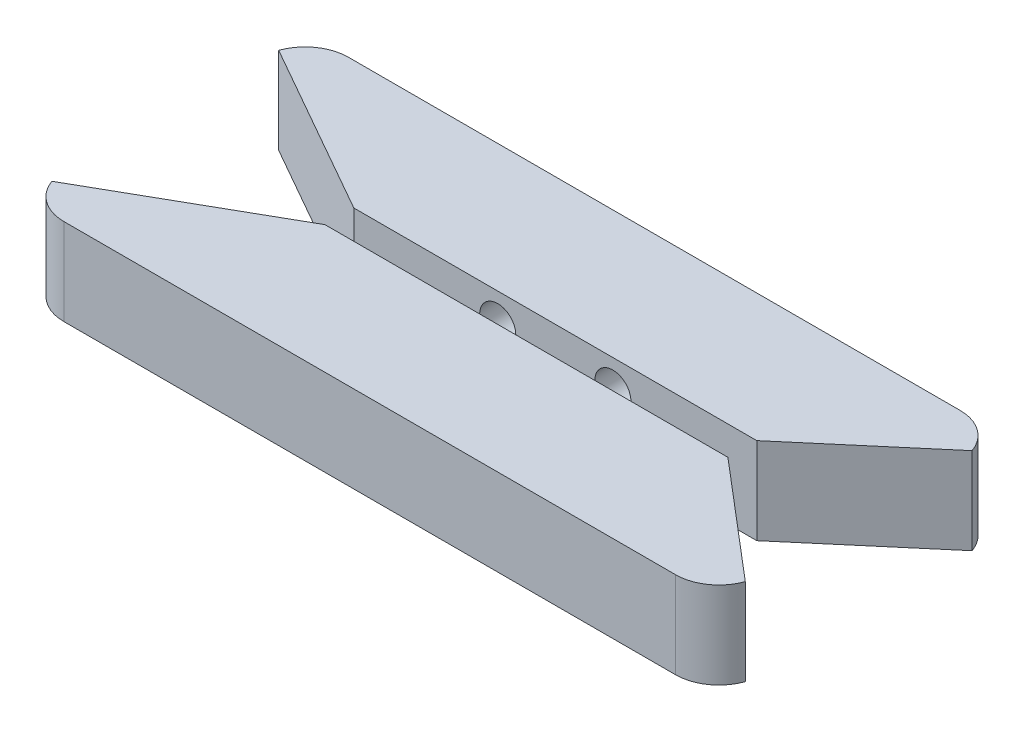
SolidWorks part; units mm, degrees
ref_plane "Front Plane" through (0, 0, 0) normal (0, 0, 1) x (1, 0, 0)
ref_plane "Top Plane" through (0, 0, 0) normal (0, 1, 0) x (1, 0, 0)
ref_plane "Right Plane" through (0, 0, 0) normal (1, 0, 0) x (0, 0, -1)
sketch "Sketch1" plane through (0, 0, 0) normal (0, 1, 0) x (1, 0, 0)
  line L0 (-51.995, 17.7) -> (44.005, 17.7)
  line L1 (-27.895, 0) -> (27.895, 0)
  line L2 (-51.995, 17.7) -> (-51.995, 13.7)
  line L3 (-51.995, 13.7) -> (-27.895, 0)
  line L4 (27.895, 0) -> (44.005, 13.7)
  line L5 (44.005, 13.7) -> (44.005, 17.7)
  dimension "D1" = 17.7
  dimension "D2" = 4
  dimension "D3" = 55.79
  dimension "D4" = 96
  dimension "D5" = 24.1
extrude "Boss-Extrude1" add sketch "Sketch1" along normal blind 12
sketch "Sketch3" plane through (0, 0, 0) normal (0, 0, 1) x (1, 0, 0)
  line L0 (0, -6.6) -> (0, 6.6) construction
  line L1 (-27.895, 12) -> (27.895, 12) construction
  circle A0 centre (-7.97, 8) radius 2.5
  circle A1 centre (7.97, 8) radius 2.5
  dimension "D1" = 5
  dimension "D2" = 4
  dimension "D3" = 15.94
extrude "Cut-Extrude1" cut sketch "Sketch3" against normal blind 8.5
fillet "Fillet1" radius 6 2 edges at (44.005, 6, -17.7) (-51.995, 6, -17.7)
ref_plane "Plane1" through (0, 0, 2) normal (0, 0, 1) x (1, 0, 0)
mirror "Mirror1" about plane through (0, 0, 2) normal (0, 0, 1) of bodies 102
